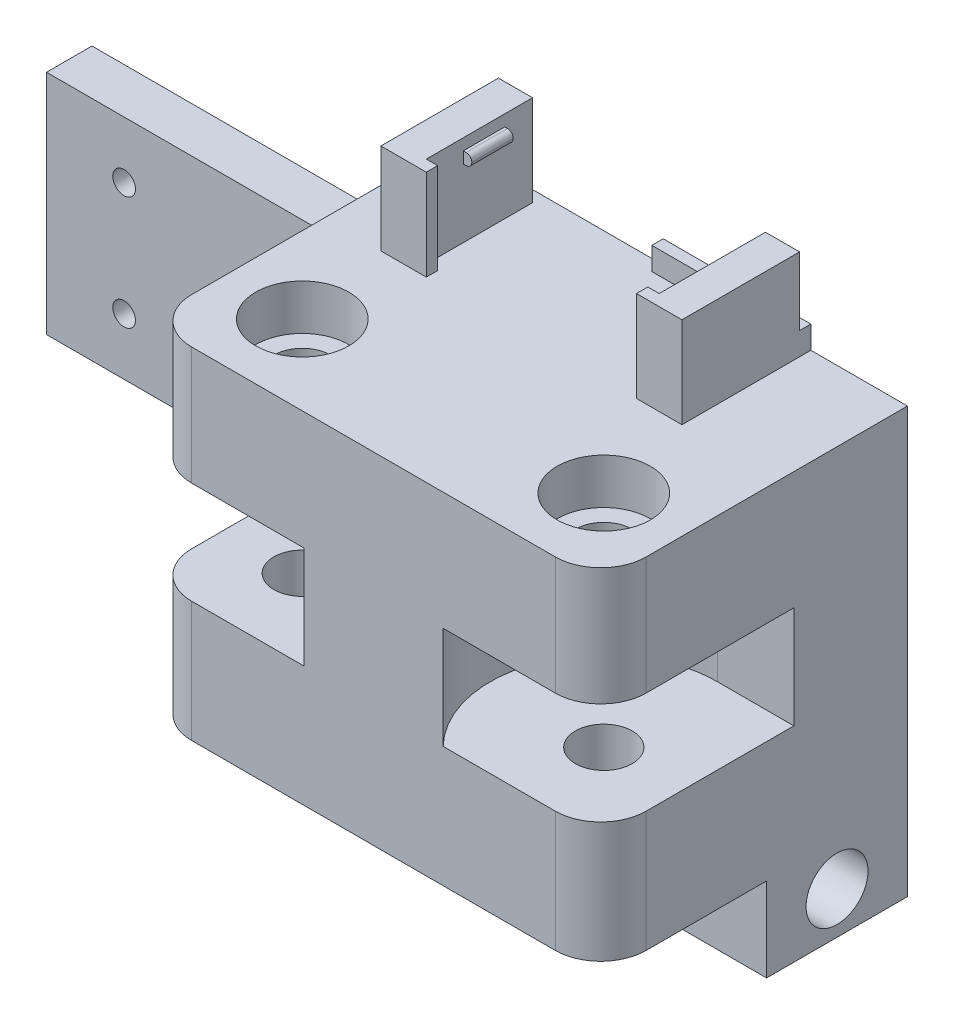
SolidWorks part; units mm, degrees
ref_plane "Front Plane" through (0, 0, 0) normal (0, 0, 1) x (1, 0, 0)
ref_plane "Top Plane" through (0, 0, 0) normal (0, 1, 0) x (1, 0, 0)
ref_plane "Right Plane" through (0, 0, 0) normal (1, 0, 0) x (0, 0, -1)
sketch "Sketch1" plane through (0, 0, 0) normal (0, 1, 0) x (1, 0, 0)
  line L1 (-22.8462, -9.1868) -> (17.1538, -9.1868)
  line L2 (-22.8462, -9.1868) -> (-22.8462, 17.8132)
  line L3 (-22.8462, 17.8132) -> (17.1538, 17.8132)
  line L4 (17.1538, -9.1868) -> (17.1538, 17.8132)
  dimension "D1" = 27
  dimension "D2" = 40
extrude "Boss-Extrude1" add sketch "Sketch1" along normal blind 30
sketch "Sketch2" plane through (0, 0, -17.8132) normal (0, 0, -1) x (-1, 0, 0)
  line L0 (2.8462, 30) -> (2.8462, 0) construction
  line L1 (-8.0864, 4) -> (-0.2064, 4)
  line L2 (-0.2064, 4) -> (-0.2064, 7)
  line L3 (-0.2064, 7) -> (-2.8664, 7)
  line L4 (-2.8664, 7) -> (-2.8664, 8.0087)
  line L5 (-2.8664, 8.0087) -> (-0.2538, 10.6287)
  line L6 (-0.2538, 10.6287) -> (5.9462, 10.6287)
  line L7 (-17.1538, 30) -> (22.8462, 30) construction
  line L8 (-17.1538, 0) -> (22.8462, 0) construction
  line L9 (-8.0864, 4) -> (-8.0864, 26)
  line L10 (-8.0864, 26) -> (-0.2064, 26)
  line L11 (-0.2064, 26) -> (-0.2064, 23)
  line L12 (-0.2064, 23) -> (-2.8664, 23)
  line L13 (-2.8664, 23) -> (-2.8664, 21.9913)
  line L14 (-2.8664, 21.9913) -> (-0.2464, 19.3787)
  line L15 (-0.2464, 19.3787) -> (5.9536, 19.3787)
  line L16 (-17.1538, 15) -> (22.8462, 15) construction
  line L17 (-17.1538, 30) -> (-17.1538, 0) construction
  line L18 (22.8462, 30) -> (22.8462, 0) construction
  line L19 (5.9387, 19.3787) -> (-0.2613, 19.3787)
  line L20 (8.5587, 21.9913) -> (5.9387, 19.3787)
  line L21 (8.5587, 23) -> (8.5587, 21.9913)
  line L22 (5.8987, 23) -> (8.5587, 23)
  line L23 (5.8987, 26) -> (5.8987, 23)
  line L24 (13.7787, 26) -> (5.8987, 26)
  line L25 (13.7787, 4) -> (13.7787, 26)
  line L26 (8.5587, 8.0087) -> (5.9462, 10.6287)
  line L27 (8.5587, 7) -> (8.5587, 8.0087)
  line L28 (5.8987, 7) -> (8.5587, 7)
  line L29 (5.8987, 4) -> (5.8987, 7)
  line L30 (13.7787, 4) -> (5.8987, 4)
  point P26 (-8.0864, 15)
  point P27 (2.8462, 15)
  point P37 (2.8462, 10.6287)
  dimension "D1" = 6.2
  dimension "D2" = 2.62
  dimension "D3" = 3.7
  dimension "D4" = 8.75
  dimension "D5" = 7.88
  dimension "D6" = 22
  dimension "D7" = 5.22
  dimension "D8" = 3
  dimension "D9" = 90
extrude "Cut-Extrude1" cut sketch "Sketch2" against normal blind 10 contours L30 L25 L24 L23 L22 L21 L20 L15 L14 L13 L12 L11 L10 L9 L1 L2 L3 L4 L5 L6 L26 L27 L28 L29 region at (-2.8462, 15.0011, -17.8132)
sketch "Sketch3" plane through (0, 0, 0) normal (0, -1, 0) x (1, 0, 0)
  line L0 (-22.8462, 9.1868) -> (17.1538, 9.1868) construction
  line L1 (17.1538, 9.1868) -> (17.1538, -17.8132) construction
  line L2 (-2.8462, 9.1868) -> (-2.8462, -17.8132) construction
  line L3 (17.1538, -17.8132) -> (-22.8462, -17.8132) construction
  circle A0 centre (10.4238, 2.1868) radius 2.5
  circle A2 centre (-16.1162, 2.1868) radius 2.5
  dimension "D1" = 5
  dimension "D3" = 7
  dimension "D4" = 6.73
extrude "Cut-Extrude2" cut sketch "Sketch3" against normal blind 30
sketch "Sketch8" plane through (0, 0, 0) normal (0, -1, 0) x (1, 0, 0)
  line L0 (3.2824, 9.1868) -> (17.1538, 9.1868)
  line L1 (-22.8462, 9.1868) -> (17.1538, 9.1868) construction
  line L2 (17.1538, 9.1868) -> (17.1538, -7.8132)
  line L3 (17.1538, 9.1868) -> (17.1538, -17.8132) construction
  line L4 (17.1538, -7.8132) -> (10.4238, -7.8132)
  line L6 (-2.8462, -17.8132) -> (-2.8462, 9.1868) construction
  line L7 (17.1538, -17.8132) -> (-22.8462, -17.8132) construction
  line L8 (-22.8462, -7.8132) -> (-16.1162, -7.8132)
  line L9 (-22.8462, 9.1868) -> (-22.8462, -7.8132)
  line L10 (-8.9747, 9.1868) -> (-22.8462, 9.1868)
  arc A0 (10.4238, -7.8132) -> (3.2824, 9.1868) centre (10.4238, 2.1868) cw
  arc A1 (-16.1162, -7.8132) -> (-8.9747, 9.1868) centre (-16.1162, 2.1868) ccw
  point P20 (10.4238, -7.3132)
  circle M6 centre (10.4238, 2.1868) radius 2.5
  circle M7 centre (-16.1162, 2.1868) radius 2.5
  line M8 (-22.8462, 9.1868) -> (-22.8462, -17.8132)
  line M10 (17.1538, -17.8132) -> (17.1538, 9.1868)
  line M11 (17.1538, 9.1868) -> (-22.8462, 9.1868)
  dimension "D1" = 10
extrude "Cut-Extrude5" cut sketch "Sketch8" against normal blind 9 from offset 10.62 contours A0 L4 M10 M11 M6 | M6 | L8 A1 M11 M8 M7 | M7 region at (10.2181, 0, 8.9483) region at (-7.1165, 0, -1.5938) region at (10.4238, 0, 2.1868) region at (-16.1162, 0, 2.1868) offset against normal yes
sketch "Sketch10" plane through (8.0864, 0, 0) normal (-1, 0, 0) x (0, 0, 1)
  line L0 (-17.8132, 30) -> (-17.8132, 0) construction
  line L1 (-17.8132, 19.62) -> (2.1868, 19.62)
  line L2 (-17.8132, 19.62) -> (-17.8132, 10.62)
  line L3 (-17.8132, 10.62) -> (2.1868, 10.62)
  line L4 (2.1868, 19.62) -> (2.1868, 10.62)
  line L6 (-7.8132, 19.62) -> (9.1868, 19.62) construction
  point P6 (2.1868, 19.62)
  point P8 (2.1868, 18.82)
  dimension "D1" = 20
extrude "Cut-Extrude7" cut sketch "Sketch10" along normal blind 6.8
sketch "Sketch12" plane through (-13.7787, 0, 0) normal (1, 0, 0) x (0, 0, -1)
  line L3 (17.8132, 10.62) -> (-2.1868, 10.62)
  line L6 (-2.1868, 10.62) -> (-2.1868, 19.62)
  line L7 (7.8132, 19.62) -> (-9.1868, 19.62) construction
  line L8 (-2.1868, 19.62) -> (17.8132, 19.62)
  line L9 (17.8132, 30) -> (17.8132, 0) construction
  line L10 (17.8132, 19.62) -> (17.8132, 10.62)
extrude "Cut-Extrude10" cut sketch "Sketch12" along normal blind 6.8
fillet "Fillet1" radius 4 4 edges at (17.1538, 5.31, 9.1868) (17.1538, 24.81, 9.1868) (-22.8462, 5.31, 9.1868) (-22.8462, 24.81, 9.1868)
sketch "Sketch13" plane through (17.1538, 0, 0) normal (1, 0, 0) x (0, 0, -1)
  line L0 (-5.1868, 0) -> (17.8132, 0) construction
  line L1 (17.8132, 30) -> (17.8132, 0) construction
  line L3 (17.8132, 0) -> (5.4132, 0)
  line L4 (17.8132, 0) -> (17.8132, -7.4)
  line L5 (17.8132, -7.4) -> (5.4132, -7.4)
  line L6 (5.4132, 0) -> (5.4132, -7.4)
  circle A0 centre (11.6132, -3.7) radius 2.725
  dimension "D1" = 6.2
  dimension "D2" = 3.7
  dimension "D3" = 5.45
  dimension "D4" = 12.4
  dimension "D5" = 7.4
extrude "Boss-Extrude2" add sketch "Sketch13" against normal up to surface (40 mm away) up to face at (-22.8462, 15.06, -3.8132)
sketch "Sketch14" plane through (0, 0, -5.4132) normal (0, 0, 1) x (1, 0, 0)
  line L0 (-22.8462, -7.4) -> (17.1538, -7.4) construction
  line L1 (-12.8462, -7.4) -> (7.1538, -7.4)
  line L2 (-12.8462, -7.4) -> (-12.8462, 0)
  line L3 (-12.8462, 0) -> (7.1538, 0)
  line L4 (7.1538, -7.4) -> (7.1538, 0)
  line L5 (-18.8462, 0) -> (13.1538, 0) construction
  line L7 (17.1538, 0) -> (17.1538, -7.4) construction
  dimension "D1" = 20
  dimension "D2" = 10
extrude "Cut-Extrude11" cut sketch "Sketch14" against normal up to next
sketch "Sketch15" plane through (0, 30, 0) normal (0, 1, 0) x (1, 0, 0)
  line L0 (-2.8462, 17.8132) -> (-2.8462, -9.1868) construction
  line L13 (17.1538, 17.8132) -> (-22.8462, 17.8132) construction
  line L14 (-18.8462, -9.1868) -> (13.1538, -9.1868) construction
  circle A4 centre (-16.1162, -2.1868) radius 4.1
  circle A5 centre (10.4238, -2.1868) radius 4.1
  dimension "D1" = 8.2
extrude "Cut-Extrude12" cut sketch "Sketch15" against normal blind 4
sketch "Sketch16" plane through (0, 0, 0) normal (0, -1, 0) x (1, 0, 0)
  line L1 (-13.749, -1.9132) -> (-11.3819, 2.1868)
  line L2 (-11.3819, 2.1868) -> (-13.749, 6.2868)
  line L3 (-13.749, 6.2868) -> (-18.4833, 6.2868)
  line L4 (-18.4833, 6.2868) -> (-20.8504, 2.1868)
  line L5 (-20.8504, 2.1868) -> (-18.4833, -1.9132)
  line L6 (-18.4833, -1.9132) -> (-13.749, -1.9132)
  line L7 (12.791, -1.9132) -> (15.1581, 2.1868)
  line L8 (15.1581, 2.1868) -> (12.791, 6.2868)
  line L9 (12.791, 6.2868) -> (8.0567, 6.2868)
  line L10 (8.0567, 6.2868) -> (5.6896, 2.1868)
  line L11 (5.6896, 2.1868) -> (8.0567, -1.9132)
  line L12 (8.0567, -1.9132) -> (12.791, -1.9132)
  circle A0 centre (10.4238, 2.1868) radius 2.5 construction
  circle A1 centre (-16.1162, 2.1868) radius 2.5 construction
  circle A2 centre (10.4238, 2.1868) radius 2.5
  circle A3 centre (-16.1162, 2.1868) radius 2.5
  circle A4 centre (-16.1162, 2.1868) radius 4.1 construction
  circle A5 centre (10.4238, 2.1868) radius 4.1 construction
  dimension "D1" = 8.2
  dimension "D2" = 8.2
extrude "Cut-Extrude13" cut sketch "Sketch16" against normal blind 4
sketch "Sketch17" plane through (0, 30, 0) normal (0, 1, 0) x (1, 0, 0)
  line L1 (8.6538, 16.8132) -> (5.6538, 16.8132)
  line L2 (8.6538, 16.8132) -> (8.6538, 7.4632)
  line L3 (8.6538, 7.4632) -> (5.6538, 7.4632)
  line L4 (-18.8462, -9.1868) -> (13.1538, -9.1868)
  line L5 (17.1538, -5.1868) -> (17.1538, 17.8132)
  line L6 (17.1538, 17.8132) -> (-22.8462, 17.8132)
  line L7 (-22.8462, 17.8132) -> (-22.8462, -5.1868)
  line L8 (-18.8462, -9.1868) -> (13.1538, -9.1868)
  line L9 (17.1538, -5.1868) -> (17.1538, 17.8132)
  line L10 (17.1538, 17.8132) -> (-22.8462, 17.8132)
  line L11 (-22.8462, 17.8132) -> (-22.8462, -5.1868)
  line L12 (5.6538, 16.8132) -> (5.6538, 7.4632)
  line L13 (-14.8462, 16.8132) -> (-17.8462, 16.8132)
  line L14 (-14.8462, 16.8132) -> (-14.8462, 7.4632)
  line L15 (-14.8462, 7.4632) -> (-17.8462, 7.4632)
  line L16 (-17.8462, 16.8132) -> (-17.8462, 7.4632)
  line L17 (8.6538, 7.4632) -> (4.6538, 7.4632)
  line L18 (8.6538, 7.4632) -> (8.6538, 6.4632)
  line L19 (8.6538, 6.4632) -> (4.6538, 6.4632)
  line L20 (4.6538, 7.4632) -> (4.6538, 6.4632)
  line L21 (-17.8462, 7.4632) -> (-13.8462, 7.4632)
  line L22 (-17.8462, 7.4632) -> (-17.8462, 6.4632)
  line L23 (-17.8462, 6.4632) -> (-13.8462, 6.4632)
  line L24 (-13.8462, 7.4632) -> (-13.8462, 6.4632)
  arc A2 (13.1538, -9.1868) -> (17.1538, -5.1868) centre (13.1538, -5.1868) ccw
  arc A3 (-22.8462, -5.1868) -> (-18.8462, -9.1868) centre (-18.8462, -5.1868) ccw
  arc A4 (13.1538, -9.1868) -> (17.1538, -5.1868) centre (13.1538, -5.1868) ccw
  arc A5 (-22.8462, -5.1868) -> (-18.8462, -9.1868) centre (-18.8462, -5.1868) ccw
  line M30 (17.1538, 17.8132) -> (-22.8462, 17.8132)
  dimension "D2" = 9.35
  dimension "D3" = 3
  dimension "D4" = 3
  dimension "D5" = 20.5
  dimension "D6" = 5
  dimension "D7" = 1
  dimension "D8" = 1
  dimension "D9" = 4
  dimension "D10" = 1
  dimension "D11" = 1
  dimension "D1" = 0
extrude "Boss-Extrude3" add sketch "Sketch17" along normal blind 8 contours L12 L3 L2 M30 | L10 L16 L15 L14 | L24 L21 L15 L22 L23 | L17 L20 L19 L18 L3 region at (7.1538, 30, -12.1382) region at (6.6538, 30, -6.9632) region at (-16.3462, 30, -12.1382) region at (-15.8462, 30, -6.9632)
sketch "Sketch20" plane through (0, 38, 0) normal (0, 1, 0) x (1, 0, 0)
  line L0 (5.6538, 16.8132) -> (5.6538, 7.4632) construction
  line L1 (5.6538, 14.3623) -> (4.9038, 14.3623)
  line L2 (5.6538, 14.3623) -> (5.6538, 10.716)
  line L3 (5.6538, 10.716) -> (4.9038, 10.716)
  line L4 (4.9038, 14.3623) -> (4.9038, 10.716)
  line L5 (-14.8462, 16.8132) -> (-14.8462, 7.4632) construction
  line L6 (-14.8462, 14.3623) -> (-14.0962, 14.3623)
  line L7 (-14.8462, 14.3623) -> (-14.8462, 10.716)
  line L8 (-14.8462, 10.716) -> (-14.0962, 10.716)
  line L9 (-14.0962, 14.3623) -> (-14.0962, 10.716)
  dimension "D1" = 0.75
  dimension "D2" = 0.75
extrude "Boss-Extrude4" add sketch "Sketch20" along normal blind 1 from offset 2 offset against normal yes
fillet "Fillet2" radius 0.5 4 edges at (-14.0962, 36, -12.5391) (4.9038, 36, -12.5391) (-14.0962, 37, -12.5391) (4.9038, 37, -12.5391)
sketch "Sketch22" plane through (0, 0, -17.8132) normal (0, 0, -1) x (-1, 0, 0)
  line L1 (-8.6538, 32) -> (4.3462, 32)
  line L2 (-8.6538, 32) -> (-8.6538, 30)
  line L3 (-8.6538, 30) -> (4.3462, 30)
  line L4 (4.3462, 32) -> (4.3462, 30)
  line L7 (-5.6538, 38) -> (-5.6538, 30) construction
  line L8 (-5.6538, 38) -> (-5.6538, 30)
  line L9 (-17.1538, 30) -> (22.8462, 30) construction
  line L11 (-8.6538, 38) -> (-8.6538, 30) construction
  dimension "D1" = 2
  dimension "D2" = 13
extrude "Boss-Extrude6" add sketch "Sketch22" along normal blind 1 from surface contours L8 L1 L2 L3 | L1 L8 L3 L4 region at (7.1538, 31, -17.8132) region at (0.6538, 31, -17.8132) starting at face at (7.1538, 34, -16.8132)
sketch "Sketch23" plane through (-22.8462, 0, 0) normal (-1, 0, 0) x (0, 0, 1)
  line L0 (-17.8132, 30) -> (-17.8132, -7.4) construction
  line L1 (-17.8132, 21.5555) -> (-13.8132, 21.5555)
  line L2 (-17.8132, 21.5555) -> (-17.8132, 1.5555)
  line L3 (-17.8132, 1.5555) -> (-13.8132, 1.5555)
  line L4 (-13.8132, 21.5555) -> (-13.8132, 1.5555)
  dimension "D1" = 20
  dimension "D2" = 4
extrude "Boss-Extrude7" add sketch "Sketch23" along normal blind 31.778
sketch "Sketch25" plane through (0, 0, -17.8132) normal (0, 0, -1) x (-1, 0, 0)
  line L0 (54.6242, 1.5555) -> (22.8462, 1.5555) construction
  line L1 (54.6242, 21.5555) -> (54.6242, 1.5555) construction
  circle A0 centre (47.7982, 16.5555) radius 1
  circle A1 centre (47.7982, 6.5555) radius 1
  dimension "D1" = 2
  dimension "D4" = 6.826
  dimension "D2" = 10
  dimension "D3" = 5
extrude "Cut-Extrude15" cut sketch "Sketch25" against normal up to next
